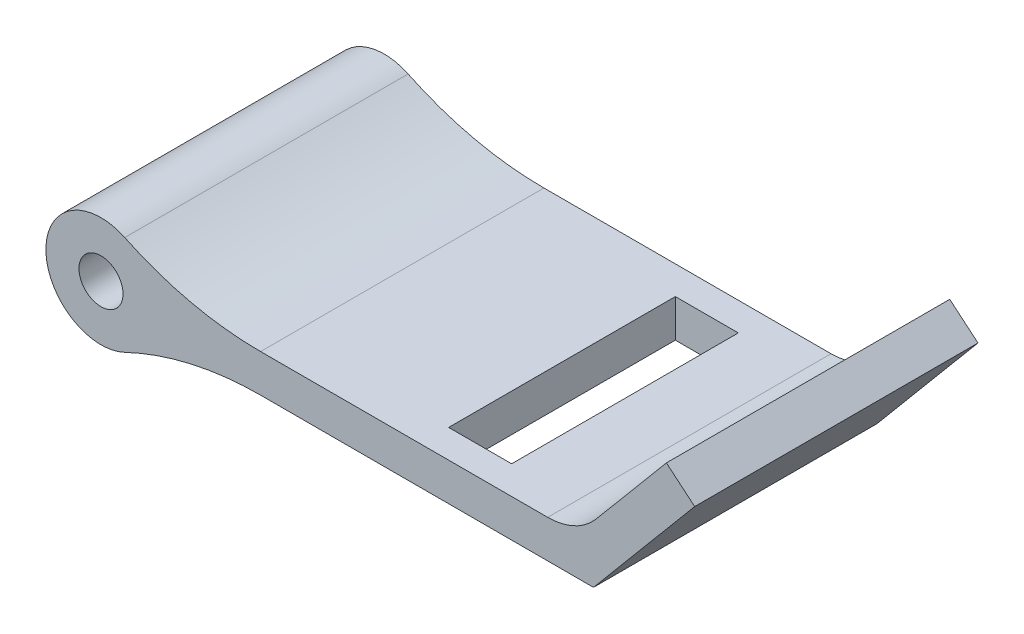
SolidWorks part; units mm, degrees
ref_plane "Front Plane" through (0, 0, 0) normal (0, 0, 1) x (1, 0, 0)
ref_plane "Top Plane" through (0, 0, 0) normal (0, 1, 0) x (1, 0, 0)
ref_plane "Right Plane" through (0, 0, 0) normal (1, 0, 0) x (0, 0, -1)
sketch "Sketch1" plane through (0, 0, 0) normal (0, 1, 0) x (1, 0, 0)
  line L1 (-7, -4.5) -> (7, -4.5)
  line L2 (-7, -4.5) -> (-7, 4.5)
  line L3 (-7, 4.5) -> (7, 4.5)
  line L4 (7, -4.5) -> (7, 4.5)
  line L5 (-7, -4.5) -> (7, 4.5) construction
  line L6 (-7, 4.5) -> (7, -4.5) construction
  line L7 (1.5, -3.6) -> (3.5, -3.6)
  line L8 (1.5, -3.6) -> (1.5, 3.6)
  line L9 (1.5, 3.6) -> (3.5, 3.6)
  line L10 (3.5, -3.6) -> (3.5, 3.6)
  line L11 (1.5, -3.6) -> (3.5, 3.6) construction
  line L12 (1.5, 3.6) -> (3.5, -3.6) construction
  point P0 (0, 0)
  point P5 (2.5, 0)
  dimension "D1" = 9
  dimension "D2" = 14
  dimension "D3" = 8.5
  dimension "D4" = 2
  dimension "D5" = 7.2
extrude "Boss-Extrude1" add sketch "Sketch1" along normal blind 1.2
sketch "Sketch2" plane through (0, 0, 0) normal (0, 0, 1) x (1, 0, 0)
  line L0 (-7, 1.2) -> (-7, 0) construction
  line L1 (-7, 1.2) -> (-7, 0) construction
  line L2 (-7, 0) -> (7, 0) construction
  circle A0 centre (-8.6439, 0.6) radius 1.75
  circle A1 centre (-8.6439, 0.6) radius 0.7
  dimension "D1" = 3.5
  dimension "D3" = 1.4
  dimension "D2" = 0.6
extrude "Boss-Extrude2" add sketch "Sketch2" along normal through all and the other way through all
fillet "Fillet1" radius 10 2 edges at (-7, 0, 0) (-7, 1.2, 0)
ref_plane "Plane1" through (3.5169, -2.951, 0) normal (0.766, -0.6428, 0) x (0, 0, -1)
sketch "Sketch3" plane through (3.5169, -2.951, 0) normal (0.766, -0.6428, 0) x (0, 0, -1)
  line L0 (-4.5, 5.4188) -> (4.5, 5.4188) construction
  line L1 (-4.5, 5.4188) -> (4.5, 5.4188) construction
  line L2 (-4.5, 4.4995) -> (4.5, 4.4995) construction
  line L3 (-4.5, 4.4995) -> (4.5, 4.4995)
  line L4 (4.5, 4.4995) -> (4.5, 9.4995)
  line L5 (-4.5, 4.4995) -> (-4.5, 9.4995)
  line L6 (4.5, 9.4995) -> (-4.5, 9.4995)
  dimension "D1" = 5
  dimension "D2" = 5
extrude "Boss-Extrude3" add sketch "Sketch3" along normal up to vertex (0.7713 mm away) and the other way blind 0.4 up to point (7, 0, 4.5)
fillet "Fillet2" radius 2 1 edges at (6.4778, 1.2, 0)
